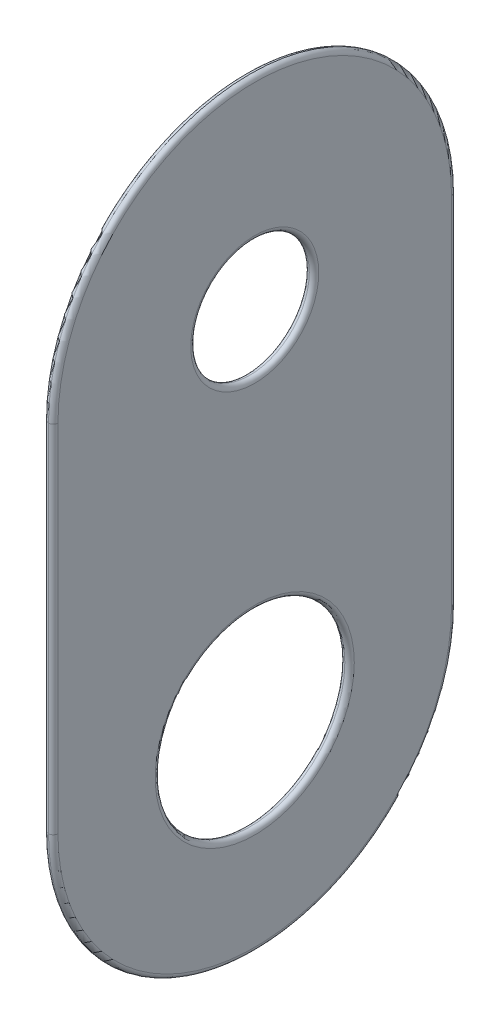
SolidWorks part; units mm, degrees
material "Plain Carbon Steel"
ref_plane "Front Plane" through (0, 0, 0) normal (0, 0, 1) x (1, 0, 0)
ref_plane "Top Plane" through (0, 0, 0) normal (0, 1, 0) x (1, 0, 0)
ref_plane "Right Plane" through (0, 0, 0) normal (1, 0, 0) x (0, 0, -1)
sketch "Sketch2" plane through (0, 0, 0) normal (1, 0, 0) x (0, 0, -1)
  line L0 (-31.7681, 0) -> (28.4393, 0) construction
  line L1 (0, 26.594) -> (0, -23.9889) construction
  line L2 (0, 9.525) -> (0, -9.525) construction
  line L3 (10.795, 9.525) -> (10.795, -9.525)
  line L4 (-10.795, 9.525) -> (-10.795, -9.525)
  circle A0 centre (0, 9.525) radius 3.175
  circle A1 centre (0, -9.525) radius 5.08
  arc A2 (10.795, 9.525) -> (-10.795, 9.525) centre (0, 9.525) ccw
  arc A3 (-10.795, -9.525) -> (10.795, -9.525) centre (0, -9.525) ccw
  point P9 (0, 0)
  dimension "D2" = 6.35
  dimension "D3" = 10.16
  dimension "D1" = 19.05
  dimension "D4" = 21.59
extrude "Boss-Extrude1" add sketch "Sketch2" along normal mid plane 0.508
fillet "Fillet1" radius 0.254 6 edges at (0.254, -9.525, -5.08) (0.254, 0, -10.795) (0.254, -20.32, 0) (0.254, 0, 10.795) (0.254, 20.32, 0) (0.254, 9.525, -3.175)
fillet "Fillet2" radius 0.254 6 edges at (-0.254, -9.525, -5.08) (-0.254, 9.525, -3.175) (-0.254, 0, 10.795) (-0.254, -20.32, 0) (-0.254, 0, -10.795) (-0.254, 20.32, 0)
